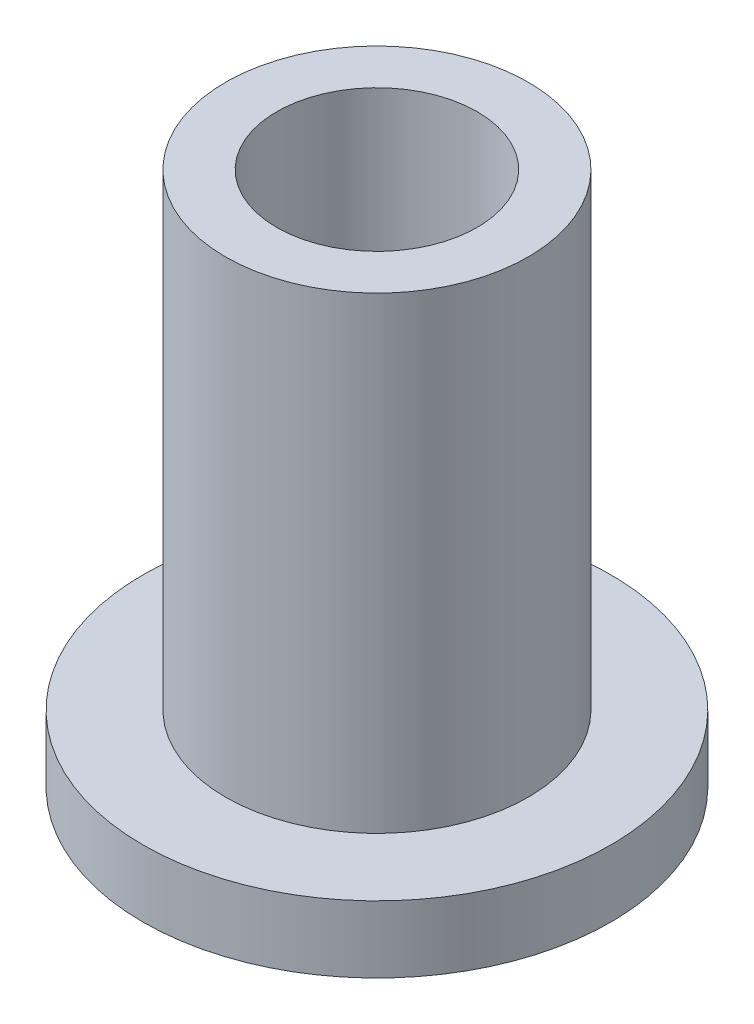
SolidWorks part; units mm, degrees
material "6061 Alloy"
ref_plane "Front Plane" through (0, 0, 0) normal (0, 0, 1) x (1, 0, 0)
ref_plane "Top Plane" through (0, 0, 0) normal (0, 1, 0) x (1, 0, 0)
ref_plane "Right Plane" through (0, 0, 0) normal (1, 0, 0) x (0, 0, -1)
sketch "Sketch1" plane through (0, 0, 0) normal (0, 1, 0) x (1, 0, 0)
  circle A0 centre (0, 0) radius 5.5562
  dimension "D1" = 11.1125
extrude "Boss-Extrude1" add sketch "Sketch1" along normal blind 1.5875
sketch "Sketch2" plane through (0, 1.5875, 0) normal (0, 1, 0) x (1, 0, 0)
  circle A1 centre (0, 0) radius 3.5941
  dimension "D2" = 7.1882
extrude "Boss-Extrude2" add sketch "Sketch2" along normal blind 11.1125 contours A1 region at (0, 1.5875, 0)
sketch "Sketch3" plane through (0, 12.7, 0) normal (0, 1, 0) x (1, 0, 0)
  circle A0 centre (0, 0) radius 2.3813
  dimension "D1" = 4.7625
extrude "Cut-Extrude1" cut sketch "Sketch3" against normal up to surface (12.7 mm away) contours A0 region at (0, 12.7, 0) up to face at (0, 0, 5.5562)
equation "\"D1@Boss-Extrude2\"=1/2-1/16"
